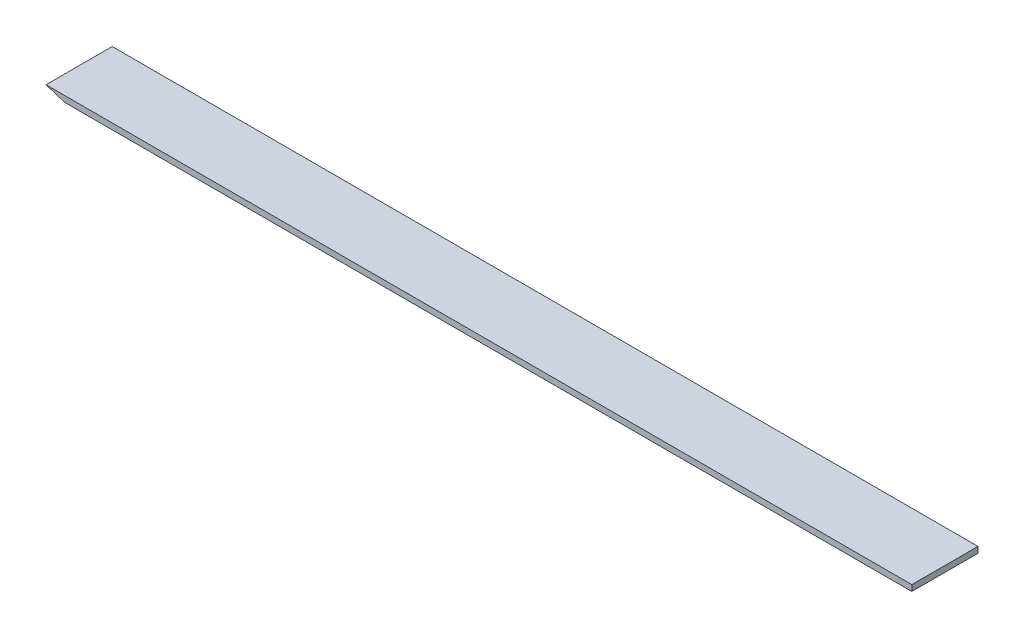
SolidWorks part; units mm, degrees
ref_plane "Front Plane" through (0, 0, 0) normal (0, 0, 1) x (1, 0, 0)
ref_plane "Top Plane" through (0, 0, 0) normal (0, 1, 0) x (1, 0, 0)
ref_plane "Right Plane" through (0, 0, 0) normal (1, 0, 0) x (0, 0, -1)
sketch "Sketch1" plane through (0, 0, 0) normal (0, 0, 1) x (1, 0, 0)
  line L0 (0, 0) -> (1308, 0)
  line L1 (1308, 0) -> (1308, -9)
  line L2 (1308, -9) -> (28, -9)
  line L3 (28, -9) -> (0, 0)
  dimension "D1" = 9
  dimension "D2" = 1280
  dimension "D3" = 28
extrude "Boss-Extrude1" add sketch "Sketch1" along normal blind 100 contours L3 L0 L1 L2
